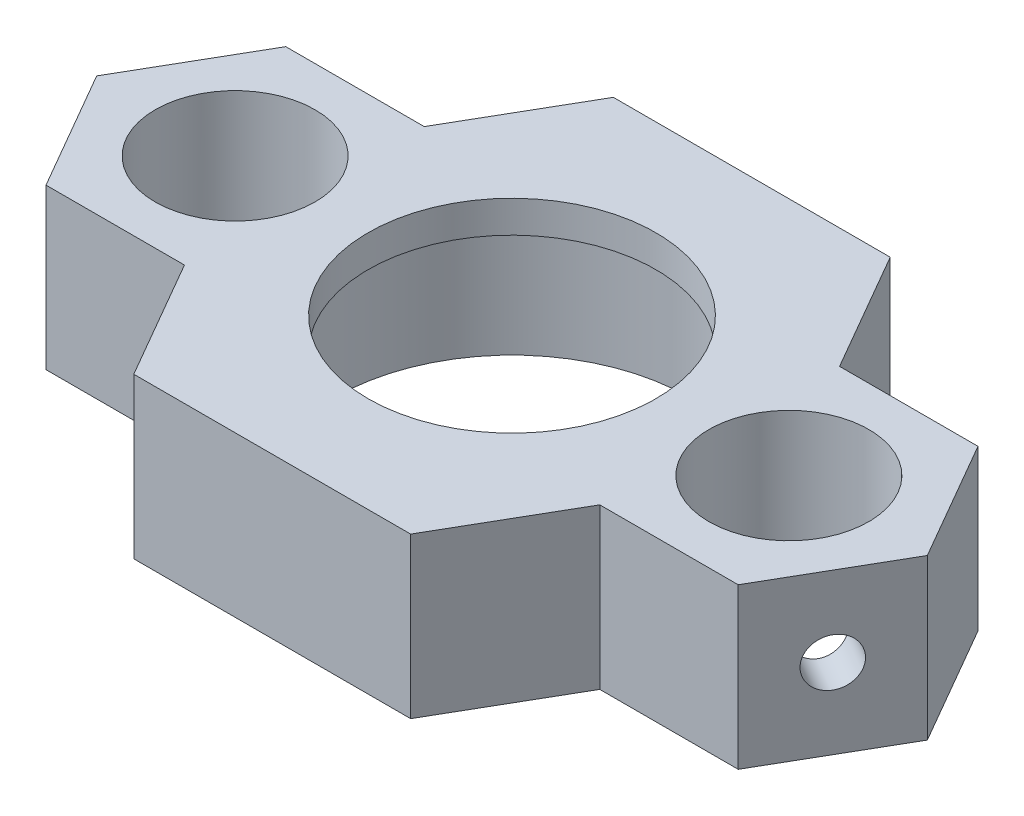
SolidWorks part; units mm, degrees
ref_plane "Front Plane" through (0, 0, 0) normal (0, 0, 1) x (1, 0, 0)
ref_plane "Top Plane" through (0, 0, 0) normal (0, 1, 0) x (1, 0, 0)
ref_plane "Right Plane" through (0, 0, 0) normal (1, 0, 0) x (0, 0, -1)
sketch "Sketch1" plane through (0, 0, 0) normal (0, 1, 0) x (1, 0, 0)
  line L0 (0, 0) -> (17.3205, 0) construction
  line L1 (17.3205, 0) -> (14.8205, 4.3301) construction
  line L2 (8.6603, 15) -> (-8.6603, 15)
  line L3 (-8.6603, 15) -> (-12.9904, 7.5)
  line L4 (-12.9904, -7.5) -> (-8.6603, -15)
  line L5 (-8.6603, -15) -> (8.6603, -15)
  line L6 (8.6603, -15) -> (12.9904, -7.5)
  line L7 (0, 15) -> (0, -15) construction
  line L8 (25.9808, 0) -> (21.6506, 7.5)
  line L9 (21.6506, 7.5) -> (12.9904, 7.5)
  line L10 (10.8253, 3.75) -> (10.6036, 3.3659)
  line L11 (10.6036, -3.3659) -> (10.8253, -3.75) construction
  line L12 (12.9904, -7.5) -> (21.6506, -7.5)
  line L13 (21.6506, -7.5) -> (25.9808, 0)
  line L14 (-21.6506, -7.5) -> (-25.9808, 0)
  line L15 (-12.9904, -7.5) -> (-21.6506, -7.5)
  line L16 (-10.6036, -3.3659) -> (-12.9904, -7.5) construction
  line L17 (-12.9904, 7.5) -> (-10.6036, 3.3659) construction
  line L18 (-21.6506, 7.5) -> (-12.9904, 7.5)
  line L19 (-25.9808, 0) -> (-21.6506, 7.5)
  line L20 (-12.9904, 7.5) -> (-14.8205, 4.3301) construction
  line L21 (-14.8205, 4.3301) -> (-17.3205, 0) construction
  line L22 (-17.3205, 0) -> (-14.8205, -4.3301) construction
  line L23 (-10.6036, 3.3659) -> (-8.6603, 0) construction
  line L24 (-8.6603, 0) -> (-10.6036, -3.3659) construction
  line L25 (-14.8205, -4.3301) -> (-12.9904, -7.5) construction
  line L26 (10.6036, 3.3659) -> (8.6603, 0) construction
  line L27 (8.6603, 0) -> (10.6036, -3.3659) construction
  line L28 (10.8253, -3.75) -> (12.9904, -7.5) construction
  line L29 (14.8205, 4.3301) -> (13.5705, 6.4952) construction
  line L30 (12.9904, 7.5) -> (8.6603, 15)
  line L31 (13.5705, -6.4952) -> (14.8205, -4.3301) construction
  line L32 (14.8205, -4.3301) -> (17.3205, 0) construction
  line L33 (12.9904, -7.5) -> (13.5705, -6.4952) construction
  line L34 (12.9904, 7.5) -> (10.8253, 3.75) construction
  line L35 (13.5705, 6.4952) -> (12.9904, 7.5) construction
  circle A0 centre (0, 0) radius 11.125
  circle A1 centre (0, 0) radius 15 construction
  circle A2 centre (17.3205, 0) radius 5
  circle A3 centre (17.3205, 0) radius 7.5 construction
  circle A4 centre (-17.3205, 0) radius 5
  dimension "D1" = 22.25
  dimension "D3" = 10
  dimension "D2" = 30
  dimension "D4" = 15
extrude "Boss-Extrude1" add sketch "Sketch1" along normal blind 8 contours L30 L2 L3 L18 L19 L14 L15 L4 L5 L6 L12 L13 L8 L9 | A0 | A4 | A2
sketch "Sketch2" plane through (0, 8, 0) normal (0, 1, 0) x (1, 0, 0)
  line L0 (-8.6603, 15) -> (-12.9904, 7.5)
  line L1 (-12.9904, 7.5) -> (-21.6506, 7.5)
  line L2 (-21.6506, 7.5) -> (-25.9808, 0)
  line L3 (-25.9808, 0) -> (-21.6506, -7.5)
  line L4 (-12.9904, -7.5) -> (-21.6506, -7.5) construction
  line L5 (-21.6506, -7.5) -> (-25.9808, 0) construction
  line L6 (-21.6506, -7.5) -> (-12.9904, -7.5)
  line L7 (-12.9904, -7.5) -> (-8.6603, -15)
  line L8 (-8.6603, -15) -> (8.6603, -15)
  line L9 (8.6603, -15) -> (12.9904, -7.5)
  line L10 (12.9904, -7.5) -> (21.6506, -7.5)
  line L11 (21.6506, -7.5) -> (25.9808, 0)
  line L12 (25.9808, 0) -> (21.6506, 7.5)
  line L13 (21.6506, 7.5) -> (12.9904, 7.5)
  line L14 (12.9904, 7.5) -> (8.6603, 15)
  line L15 (8.6603, 15) -> (-8.6603, 15)
  circle A0 centre (0, 0) radius 9
  circle A1 centre (-17.3205, 0) radius 5
  circle A2 centre (17.3205, 0) radius 5
  circle A3 centre (-17.3205, 0) radius 5 construction
  circle A4 centre (17.3205, 0) radius 5 construction
  dimension "D1" = 18
extrude "Boss-Extrude2" add sketch "Sketch2" along normal blind 2
sketch "Sketch4" plane through (-19.4856, 0, 11.25) normal (-0.866, 0, 0.5) x (0.5, 0, 0.866)
  line L0 (-8.6603, 10) -> (-8.6603, 0) construction
  line L1 (-12.9904, 10) -> (-4.3301, 10) construction
  line L2 (-4.3301, 0) -> (-12.9904, 0) construction
  line L3 (-12.9904, 5) -> (-4.3301, 5) construction
  line L4 (-12.9904, 10) -> (-12.9904, 0) construction
  line L5 (-4.3301, 10) -> (-4.3301, 0) construction
  circle A0 centre (-8.6603, 5) radius 1.5
  dimension "D1" = 3
extrude "Cut-Extrude1" cut sketch "Sketch4" against normal up to surface and the other way through all up to face at (-17.3205, 0, -5)
sketch "Sketch5" plane through (19.4856, 0, 11.25) normal (0.866, 0, 0.5) x (0.5, 0, -0.866)
  line L0 (8.6603, 10) -> (8.6603, 0) construction
  line L1 (4.3301, 10) -> (12.9904, 10) construction
  line L2 (4.3301, 0) -> (12.9904, 0) construction
  line L3 (4.3301, 5) -> (12.9904, 5) construction
  line L4 (4.3301, 10) -> (4.3301, 0) construction
  line L5 (12.9904, 10) -> (12.9904, 0) construction
  circle A0 centre (8.6603, 5) radius 1.5
  dimension "D1" = 3
extrude "Cut-Extrude2" cut sketch "Sketch5" against normal up to surface (2.7303 mm away) up to face at (17.3205, 0, 5)
